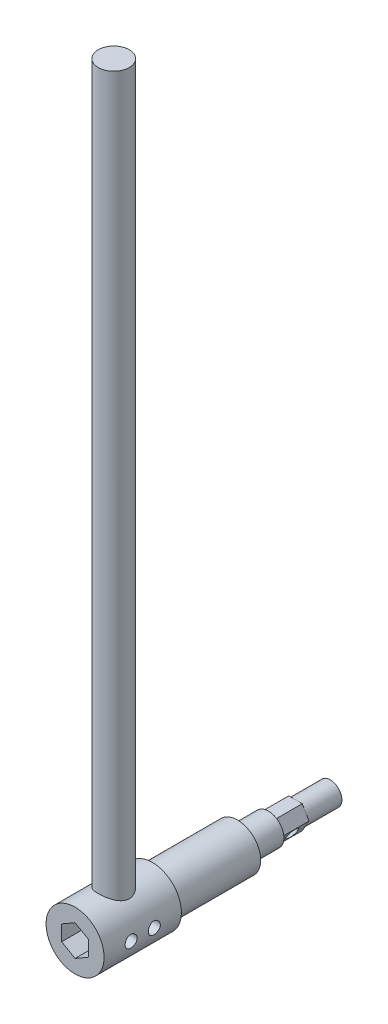
SolidWorks part; units mm, degrees
ref_plane "Front Plane" through (0, 0, 0) normal (0, 0, 1) x (1, 0, 0)
ref_plane "Top Plane" through (0, 0, 0) normal (0, 1, 0) x (1, 0, 0)
ref_plane "Right Plane" through (0, 0, 0) normal (1, 0, 0) x (0, 0, -1)
sketch "Sketch1" plane through (0, 0, 0) normal (0, 0, 1) x (1, 0, 0)
  line L3 (0, 4) -> (3.4641, 2)
  line L4 (3.4641, 2) -> (3.4641, -2)
  line L5 (3.4641, -2) -> (0, -4)
  line L12 (0, -4) -> (-3.4641, -2)
  line L13 (-3.4641, -2) -> (-3.4641, 2)
  line L14 (-3.4641, 2) -> (0, 4)
  circle A0 centre (0, 0) radius 7.5
  point P7 (0, 0)
  point P12 (0, 0)
  point P16 (0, 0)
extrude "Boss-Extrude1" add sketch "Sketch1" along normal blind 20
ref_plane "Plane2" through (0, 192.5, 0) normal (0, 1, 0) x (1, 0, 0)
sketch "Sketch6" plane through (0, 192.5, 0) normal (0, 1, 0) x (1, 0, 0)
  line L0 (0, 0) -> (0, -20) construction
  line L1 (-7.5, -20) -> (7.5, -20) construction
  circle A0 centre (0, -10) radius 4
extrude "Boss-Extrude3" add sketch "Sketch6" against normal up to surface (185 mm away) up to face at (7.5, 0, 20)
ref_plane "Plane4" through (0, 0, 0) normal (-1, 0, 0) x (0, 0, 1)
sketch "Sketch8" plane through (0, 0, 0) normal (-1, 0, 0) x (0, 0, 1)
  line L0 (20, 0) -> (0, 0) construction
  line L1 (20, -7.5) -> (20, 7.5) construction
  circle A0 centre (7, 0) radius 1.55
  circle A1 centre (13, 0) radius 1.55
extrude "Cut-Extrude1" cut sketch "Sketch8" against normal blind 7.5 and the other way blind 7.5
sketch "Sketch11" plane through (0, 0, 0) normal (0, 0, -1) x (-1, 0, 0)
  circle A0 centre (0, 0) radius 6
extrude "Boss-Extrude12" add sketch "Sketch11" along normal blind 22
sketch "Sketch12" plane through (0, 0, -22) normal (0, 0, -1) x (-1, 0, 0)
  circle A0 centre (0, 0) radius 4
extrude "Boss-Extrude13" add sketch "Sketch12" along normal blind 8
sketch "Sketch13" plane through (0, 0, -30) normal (0, 0, -1) x (-1, 0, 0)
  line L0 (3.5, 0) -> (-3.5, 0) construction
  line L1 (-1.75, -3.0311) -> (1.75, 3.0311) construction
  line L2 (1.75, -3.0311) -> (-1.75, 3.0311) construction
  line L3 (1.75, 3.0311) -> (-1.75, 3.0311)
  line L4 (-1.75, 3.0311) -> (-3.5, 0)
  line L5 (-3.5, 0) -> (-1.75, -3.0311)
  line L6 (-1.75, -3.0311) -> (1.75, -3.0311)
  line L7 (1.75, -3.0311) -> (3.5, 0)
  line L8 (3.5, 0) -> (1.75, 3.0311)
  point P6 (0, 0)
  point P9 (0, 0)
  point P12 (0, 0)
extrude "Boss-Extrude14" add sketch "Sketch13" along normal blind 7 contours L4 L5 L6 L7 L8 L3
sketch "Sketch14" plane through (2.625, -1.5155, 0) normal (0.866, -0.5, 0) x (0, 0, -1)
  line L0 (30, 0) -> (37, 0) construction
  line L1 (30, 1.75) -> (30, -1.75) construction
  line L2 (37, 1.75) -> (37, -1.75) construction
  circle A0 centre (33.5, 0) radius 1.55
extrude "Cut-Extrude2" cut sketch "Sketch14" against normal blind 6.1
sketch "Sketch15" plane through (0, 0, -37) normal (0, 0, -1) x (-1, 0, 0)
  circle A0 centre (0, 0) radius 3
extrude "Boss-Extrude15" add sketch "Sketch15" along normal blind 9
